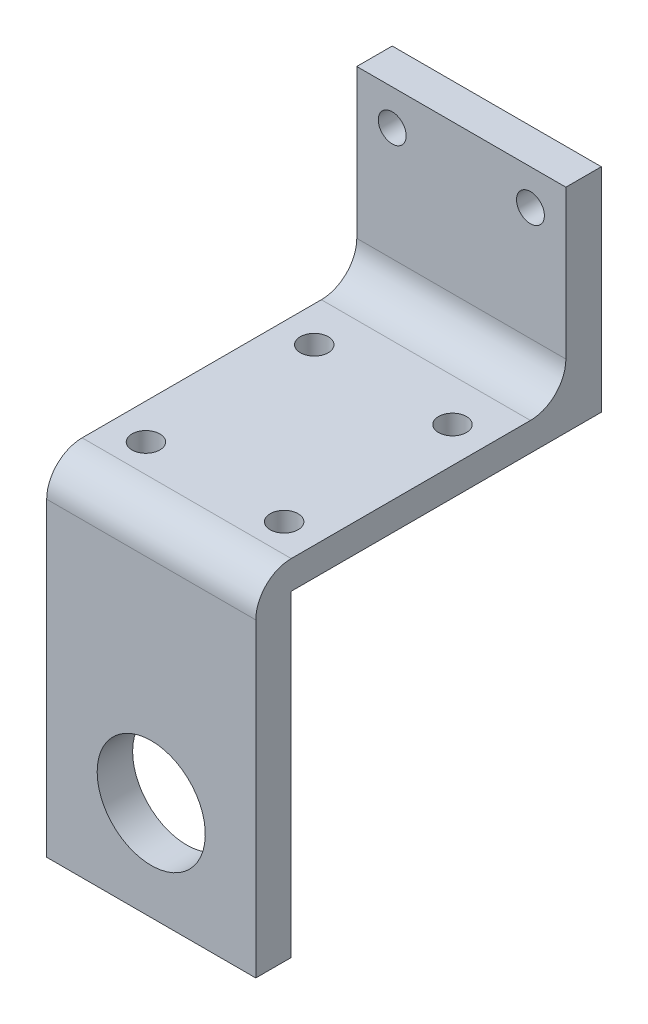
SolidWorks part; units mm, degrees
ref_plane "Front Plane" through (0, 0, 0) normal (0, 0, 1) x (1, 0, 0)
ref_plane "Top Plane" through (0, 0, 0) normal (0, 1, 0) x (1, 0, 0)
ref_plane "Right Plane" through (0, 0, 0) normal (1, 0, 0) x (0, 0, -1)
sketch "Sketch2" plane through (0, 0, 0) normal (1, 0, 0) x (0, 0, -1)
  line L3 (2.7998, -8.8508) -> (2.7998, 17.5652)
  line L4 (2.7998, 17.5652) -> (7.8798, 17.5652)
  line L5 (7.8798, 17.5652) -> (7.8798, -12.9148)
  line L6 (7.8798, -12.9148) -> (-41.6502, -12.9148)
  line L12 (2.7998, -8.8508) -> (-41.6502, -8.8508)
  line L13 (-41.6502, -8.8508) -> (-41.6502, -12.9148)
  line L15 (-41.6502, -12.9148) -> (-36.5702, -12.9148)
  line L16 (-41.6502, -12.9148) -> (-41.6502, -58.3808)
  line L17 (-41.6502, -58.3808) -> (-36.5702, -58.3808)
  line L18 (-36.5702, -12.9148) -> (-36.5702, -58.3808)
  dimension "D1" = 49.53
  dimension "D2" = 5.08
  dimension "D3" = 4.064
  dimension "D4" = 30.48
  dimension "D5" = 5.08
  dimension "D6" = 45.466
extrude "Boss-Extrude1" add sketch "Sketch2" along normal blind 29.972 contours L18 L6 L16 L17 | L3 L4 L5 L6 L13 L12 region at (0, -35.6478, 39.1102)
fillet "Fillet2" radius 5.08 2 edges at (14.986, -8.8508, -2.7998) (14.986, -8.8508, 41.6502)
sketch "Sketch3" plane through (0, 0, -7.8798) normal (0, 0, -1) x (-1, 0, 0)
  line L2 (-29.972, 17.5652) -> (0, 17.5652) construction
  circle A0 centre (-24.892, 12.4852) radius 2
  circle A1 centre (-5.08, 12.4852) radius 2
  circle A2 centre (-5.08, -11.6448) radius 4
  circle A3 centre (-24.892, -11.6448) radius 4
  dimension "D1" = 5.08
  dimension "D4" = 4
  dimension "D5" = 4
  dimension "D6" = 8
  dimension "D7" = 8
  dimension "D2" = 5.08
  dimension "D3" = 5.08
  dimension "D8" = 24.13
extrude "Cut-Extrude1" cut sketch "Sketch3" against normal up to surface (5.08 mm away) up to face at (14.986, 6.8972, -2.7998)
sketch "Sketch4" plane through (0, -12.9148, 0) normal (0, -1, 0) x (1, 0, 0)
  line L3 (29.972, -7.8798) -> (29.972, 36.5702) construction
  line L4 (0, -7.8798) -> (0, 36.5702) construction
  circle A0 centre (24.892, 8.3762) radius 2
  circle A1 centre (5.08, 8.3762) radius 2
  circle A2 centre (24.892, 32.5062) radius 2
  circle A3 centre (5.08, 32.5062) radius 2
  dimension "D1" = 4
  dimension "D2" = 4
  dimension "D3" = 4
  dimension "D4" = 4
  dimension "D5" = 5.08
  dimension "D6" = 5.08
  dimension "D7" = 24.13
  dimension "D8" = 16.256
extrude "Cut-Extrude2" cut sketch "Sketch4" against normal blind 29.972
sketch "Sketch5" plane through (0, 0, 36.5702) normal (0, 0, -1) x (-1, 0, 0)
  line L0 (-29.972, -58.3808) -> (0, -58.3808) construction
  circle A0 centre (-14.986, -44.1568) radius 7.75
  point P5 (-14.986, -58.3808)
  dimension "D1" = 15.5
  dimension "D2" = 31.242
extrude "Cut-Extrude3" cut sketch "Sketch5" against normal up to surface (5.08 mm away) up to face at (14.986, -36.1558, 41.6502)
